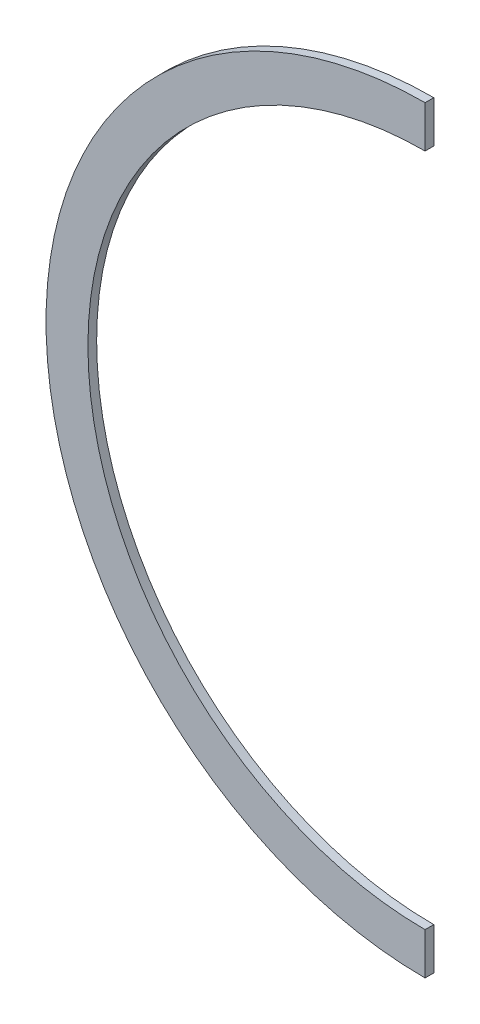
SolidWorks part; units mm, degrees
material "Balsa"
ref_plane "Front Plane" through (0, 0, 0) normal (0, 0, 1) x (1, 0, 0)
ref_plane "Top Plane" through (0, 0, 0) normal (0, 1, 0) x (1, 0, 0)
ref_plane "Right Plane" through (0, 0, 0) normal (1, 0, 0) x (0, 0, -1)
sketch "Sketch1" plane through (0, 0, 0) normal (0, 0, 1) x (1, 0, 0)
  line L0 (0, 0) -> (0, 499.9473) construction
  line L1 (0, -114.7984) -> (0, -129.4545) construction
  line L2 (0, -374.4718) -> (0, 404.2655) construction
  line L3 (-1.651, 142.9921) -> (-1.651, 150.6121) construction
  line L4 (1.651, 142.9921) -> (1.651, 150.6121) construction
  line L5 (-1.651, 142.9921) -> (1.651, 142.9921) construction
  line L6 (136.2041, -53.806) -> (0.0002, 24.7625) construction
  line L7 (-136.2076, -53.7991) -> (0.0002, 24.7625) construction
  line L8 (136.2041, -53.806) -> (0.0002, 24.7625) construction
  line L9 (-136.2076, -53.7991) -> (0.0002, 24.7625) construction
  line L10 (-125.0584, -45.4626) -> (-118.4576, -41.6554) construction
  line L11 (-123.6259, -48.4483) -> (-116.8078, -44.5157) construction
  line L12 (-118.4576, -41.6554) -> (-116.8078, -44.5157) construction
  line L13 (-124.1455, -48.7479) -> (-123.6847, -48.4822) construction
  line L14 (-123.6847, -48.4822) -> (-123.6259, -48.4483) construction
  line L15 (-125.7952, -45.8876) -> (-125.1113, -45.4931) construction
  line L16 (-125.1113, -45.4931) -> (-125.0584, -45.4626) construction
  line L17 (125.4797, -45.7137) -> (125.1075, -45.499) construction
  line L18 (123.8298, -48.5739) -> (123.6807, -48.488) construction
  line L19 (117.0223, -44.647) -> (118.6722, -41.7868) construction
  line L20 (123.6807, -48.488) -> (123.6228, -48.4545) construction
  line L21 (123.6228, -48.4545) -> (117.0223, -44.647) construction
  line L22 (125.1075, -45.499) -> (125.0554, -45.4689) construction
  line L23 (125.0554, -45.4689) -> (118.6722, -41.7868) construction
  line L24 (-107.079, -46.8884) -> (-120.3798, -54.5735)
  line L25 (-108.6638, -44.1348) -> (-121.9647, -51.8199)
  line L28 (-115.4206, -47.9666) -> (-121.9445, -51.7361) construction
  line L29 (-120.2754, -54.5131) -> (-108.646, -44.1245) construction
  line L30 (-114.4607, -49.3188) -> (-122.1124, -53.7399) construction
  line L31 (-113.7686, -50.8257) -> (-120.3665, -54.6379) construction
  line L32 (-115.4206, -47.9666) -> (-113.7686, -50.8257) construction
  line L33 (106.3137, -46.4532) -> (129.9098, -60.0883)
  line L34 (107.9004, -43.7007) -> (131.505, -57.3407)
  line L35 (129.9098, -60.0883) -> (131.505, -57.3407)
  line L36 (129.9098, -60.0883) -> (131.505, -57.3407) construction
  line L37 (107.9004, -43.7007) -> (131.505, -57.3407) construction
  line L38 (106.3137, -46.4532) -> (129.9098, -60.0883) construction
  line L39 (129.9098, -60.0883) -> (107.9004, -43.7007) construction
  line L40 (118.9051, -51.8945) -> (101.8722, -42.0519) construction
  line L41 (120.3631, -54.6438) -> (113.7655, -50.8313)
  line L42 (122.0152, -51.7848) -> (122.0057, -51.7794) construction
  line L43 (113.7655, -50.8313) -> (115.4176, -47.9723)
  line L44 (122.0057, -51.7794) -> (121.9413, -51.7421) construction
  line L45 (121.9413, -51.7421) -> (115.4176, -47.9723)
  line L46 (-108.6638, -44.1348) -> (-121.9647, -51.8199)
  line L47 (-107.079, -46.8884) -> (-120.3798, -54.5735)
  arc A0 (-1.651, 150.6121) -> (-125.0584, -45.4626) centre (0, 12.7) ccw
  circle A1 centre (0, 12.7) radius 120.904
  arc A2 (0, 150.622) -> (-1.651, 150.6121) centre (0, 12.7) ccw
  circle A3 centre (0, 12.7) radius 137.922 construction
  arc A4 (1.651, 150.6121) -> (0, 150.622) centre (0, 12.7) ccw
  arc A5 (-124.3508, -46.9604) -> (-123.6259, -48.4483) centre (0, 12.7) ccw
  arc A6 (-123.6259, -48.4483) -> (-121.9445, -51.7361) centre (0, 12.7) ccw
  arc A7 (-125.0584, -45.4626) -> (-124.3508, -46.9604) centre (0, 12.7) ccw
  arc A8 (124.3477, -46.9667) -> (125.0554, -45.4689) centre (0, 12.7) ccw
  arc A9 (125.0554, -45.4689) -> (1.651, 150.6121) centre (0, 12.7) ccw
  arc A10 (123.6228, -48.4545) -> (124.3477, -46.9667) centre (0, 12.7) ccw
  arc A11 (-121.9153, -51.7914) -> (-121.1641, -53.1919) centre (0, 12.7) ccw
  arc A12 (-120.3665, -54.6379) -> (120.3631, -54.6438) centre (0, 12.7) ccw
  arc A13 (-121.9445, -51.7361) -> (-121.9153, -51.7914) centre (0, 12.7) ccw
  arc A14 (-121.1641, -53.1919) -> (-120.3827, -54.6089) centre (0, 12.7) ccw
  arc A15 (-120.3827, -54.6089) -> (-120.397, -54.5834) centre (0, 12.7) ccw construction
  arc A16 (-120.397, -54.5834) -> (-120.3665, -54.6379) centre (0, 12.7) ccw construction
  arc A17 (120.3936, -54.5893) -> (121.0149, -53.4654) centre (0, 12.7) ccw construction
  arc A18 (121.9413, -51.7421) -> (123.6228, -48.4545) centre (0, 12.7) ccw
  arc A19 (120.3631, -54.6438) -> (120.3936, -54.5893) centre (0, 12.7) ccw construction
  arc A20 (121.0149, -53.4654) -> (121.9121, -51.7974) centre (0, 12.7) ccw construction
  arc A21 (121.9121, -51.7974) -> (121.9413, -51.7421) centre (0, 12.7) ccw construction
  spline S0 degree 3 poles (106.3137, -46.4532) (106.8426, -45.5357) (107.3715, -44.6182) (107.9004, -43.7007) knots 0 0 0 0 1 1 1 1 weights 1 1 1 1
  spline S1 degree 3 poles (-66.0123, 133.6164) (-70.0128, 131.4329) (-73.8716, 129.0699) (-81.3156, 123.9975) (-84.9009, 121.288) (-91.7995, 115.5249) (-95.113, 112.4712) (-99.0811, 108.4341) (-99.866, 107.6157) (-101.4182, 105.9565) (-102.1865, 105.1147) (-104.4569, 102.5643) (-105.9223, 100.8334) (-110.1768, 95.5512) (-115.4725, 88.2691) (-120.0285, 80.5179) (-123.1654, 74.5269) (-124.1643, 72.5002) (-125.5914, 69.415) (-126.0551, 68.3791) (-126.9587, 66.292) (-127.3989, 65.2397) (-129.5278, 59.9684) (-131.0098, 55.7) (-133.5456, 47.0638) (-134.5993, 42.696) (-136.2795, 33.8613) (-136.906, 29.3944) (-137.415, 23.7472) (-137.5031, 22.6146) (-137.6514, 20.3429) (-137.7116, 19.2049) (-137.8496, 15.7999) (-137.8852, 13.5361) (-137.8263, 6.7629) (-137.3062, -2.2197) (-135.9163, -11.1068) (-134.5433, -17.7359) (-134.0304, -19.9395) (-132.8922, -24.3345) (-132.2653, -26.5303) (-130.2347, -33.03) (-128.6774, -37.2656) (-126.1245, -43.2881) (-125.286, -45.1501) (-124.4066, -46.9926) knots 0 0 0 0 0.03125 0.03125 0.0625 0.0625 0.09375 0.09375 0.101563 0.101563 0.109375 0.109375 0.125 0.125 0.15625 0.1875 0.1875 0.203125 0.203125 0.210938 0.210938 0.21875 0.21875 0.25 0.25 0.28125 0.28125 0.3125 0.3125 0.320313 0.320313 0.328125 0.328125 0.34375 0.34375 0.375 0.40625 0.40625 0.421875 0.421875 0.4375 0.4375 0.46875 0.46875 0.48295 0.48295 0.48295 0.48295 construction
  spline S2 degree 3 poles (-1557.5256, 1030.3086) (-495.2142, -0.1753) (-82.1366, -210.7146) (81.4542, -98.9353) (85.033, -96.2237) (91.9188, -90.4573) (95.2258, -87.4025) (99.1858, -83.3647) (99.9691, -82.5461) (101.5182, -80.8868) (102.2849, -80.0449) (104.5506, -77.4941) (106.013, -75.7632) (110.2586, -70.4809) (112.9006, -66.8403) (117.8152, -59.3254) (120.0877, -55.4512) (123.2166, -49.4629) (124.2129, -47.4373) (125.6361, -44.3538) (126.0986, -43.3185) (126.9997, -41.2327) (127.4386, -40.181) (129.5618, -34.9121) (131.0396, -30.646) (133.5674, -22.0152) (134.6173, -17.6505) (136.2906, -8.8227) (136.914, -4.3596) (137.4197, 1.2823) (137.5071, 2.4139) (137.6542, 4.6834) (137.7138, 5.8206) (137.85, 9.2232) (137.8846, 11.4853) (137.8228, 18.2533) (137.2995, 27.2283) (135.9081, 36.1069) (134.5347, 42.7292) (134.0218, 44.9305) (132.8839, 49.3207) (132.2571, 51.5145) (130.2267, 58.0093) (128.67, 62.2416) (125.1615, 70.5162) (123.2097, 74.5586) (118.9108, 82.4534) (116.5637, 86.3058) (113.3753, 90.999) (112.7241, 91.9325) (111.3996, 93.7822) (110.7272, 94.697) (108.6802, 97.4113) (107.2757, 99.181) (102.9447, 104.3725) (96.8571, 110.9816) (90.1513, 116.9722) (84.8861, 121.2292) (83.0917, 122.6088) (80.3399, 124.6181) (79.4113, 125.2786) (77.543, 126.5731) (76.6028, 127.2075) (71.8708, 130.3161) (67.9881, 132.6004) (60.0328, 136.7739) (55.9603, 138.6631) (47.6249, 142.0446) (43.3619, 143.537) (37.9102, 145.1462) (36.8136, 145.4551) (34.6205, 146.0438) (33.5224, 146.3241) (30.2234, 147.1229) (28.0179, 147.5997) (21.3832, 148.8649) (16.9358, 149.4889) (7.993, 150.3014) (3.4975, 150.4899) (-3.2824, 150.4396) (-5.5486, 150.3672) (-10.0934, 150.1088) (-12.3559, 149.9236) (-19.101, 149.2046) (-23.5473, 148.5072) (-32.3412, 146.6856) (-36.6887, 145.5614) (-43.1354, 143.5526) (-45.2718, 142.8291) (-49.5193, 141.273) (-51.6323, 140.4395) (-274.1905, 46.1884) (-224.836, -608.7963) (101.1574, -1839.6029) knots -1.31339 -1.31339 -1.31339 -1.31339 0.03125 0.03125 0.0625 0.0625 0.09375 0.09375 0.101563 0.101563 0.109375 0.109375 0.125 0.125 0.15625 0.15625 0.1875 0.1875 0.203125 0.203125 0.210938 0.210938 0.21875 0.21875 0.25 0.25 0.28125 0.28125 0.3125 0.3125 0.320313 0.320313 0.328125 0.328125 0.34375 0.34375 0.375 0.40625 0.40625 0.421875 0.421875 0.4375 0.4375 0.46875 0.46875 0.5 0.5 0.53125 0.53125 0.539062 0.539062 0.546875 0.546875 0.5625 0.5625 0.59375 0.625 0.625 0.640625 0.640625 0.648437 0.648437 0.65625 0.65625 0.6875 0.6875 0.71875 0.71875 0.75 0.75 0.757812 0.757812 0.765625 0.765625 0.78125 0.78125 0.8125 0.8125 0.84375 0.84375 0.859375 0.859375 0.875 0.875 0.90625 0.90625 0.9375 0.9375 0.953125 0.953125 0.96875 0.96875 2.612134 2.612134 2.612134 2.612134 only from (66.1767, -108.566) to (-66.0123, 133.6164)
  spline S3 degree 3 poles (66.1767, -108.566) (70.1708, -106.3789) (74.0231, -104.0129) (81.4542, -98.9353) (85.033, -96.2237) (91.9188, -90.4573) (95.2258, -87.4025) (99.1858, -83.3647) (99.9691, -82.5461) (101.5182, -80.8868) (102.2849, -80.0449) (104.5506, -77.4941) (106.013, -75.7632) (110.2586, -70.4809) (112.9006, -66.8403) (117.8152, -59.3254) (120.0877, -55.4512) (123.2166, -49.4629) (124.2129, -47.4373) (125.6361, -44.3538) (126.0986, -43.3185) (126.9997, -41.2327) (127.4386, -40.181) (129.5618, -34.9121) (131.0396, -30.646) (133.5674, -22.0152) (134.6173, -17.6505) (136.2906, -8.8227) (136.914, -4.3596) (137.4197, 1.2823) (137.5071, 2.4139) (137.6542, 4.6834) (137.7138, 5.8206) (137.85, 9.2232) (137.8846, 11.4853) (137.8228, 18.2533) (137.2995, 27.2283) (135.9081, 36.1069) (134.5347, 42.7292) (134.0218, 44.9305) (132.8839, 49.3207) (132.2571, 51.5145) (130.2267, 58.0093) (128.67, 62.2416) (125.1615, 70.5162) (123.2097, 74.5586) (118.9108, 82.4534) (116.5637, 86.3058) (113.3753, 90.999) (112.7241, 91.9325) (111.3996, 93.7822) (110.7272, 94.697) (108.6802, 97.4113) (107.2757, 99.181) (102.9447, 104.3725) (96.8571, 110.9816) (90.1513, 116.9722) (84.8861, 121.2292) (83.0917, 122.6088) (80.3399, 124.6181) (79.4113, 125.2786) (77.543, 126.5731) (76.6028, 127.2075) (71.8708, 130.3161) (67.9881, 132.6004) (60.0328, 136.7739) (55.9603, 138.6631) (47.6249, 142.0446) (43.3619, 143.537) (37.9102, 145.1462) (36.8136, 145.4551) (34.6205, 146.0438) (33.5224, 146.3241) (30.2234, 147.1229) (28.0179, 147.5997) (21.3832, 148.8649) (16.9358, 149.4889) (7.993, 150.3014) (3.4975, 150.4899) (-3.2824, 150.4396) (-5.5486, 150.3672) (-10.0934, 150.1088) (-12.3559, 149.9236) (-19.101, 149.2046) (-23.5473, 148.5072) (-32.3412, 146.6856) (-36.6887, 145.5614) (-43.1354, 143.5526) (-45.2718, 142.8291) (-49.5193, 141.273) (-51.6323, 140.4395) (-57.9206, 137.7764) (-62.0153, 135.798) (-66.0123, 133.6164) knots 0 0 0 0 0.03125 0.03125 0.0625 0.0625 0.09375 0.09375 0.101563 0.101563 0.109375 0.109375 0.125 0.125 0.15625 0.15625 0.1875 0.1875 0.203125 0.203125 0.210938 0.210938 0.21875 0.21875 0.25 0.25 0.28125 0.28125 0.3125 0.3125 0.320313 0.320313 0.328125 0.328125 0.34375 0.34375 0.375 0.40625 0.40625 0.421875 0.421875 0.4375 0.4375 0.46875 0.46875 0.5 0.5 0.53125 0.53125 0.539062 0.539062 0.546875 0.546875 0.5625 0.5625 0.59375 0.625 0.625 0.640625 0.640625 0.648437 0.648437 0.65625 0.65625 0.6875 0.6875 0.71875 0.71875 0.75 0.75 0.757812 0.757812 0.765625 0.765625 0.78125 0.78125 0.8125 0.8125 0.84375 0.84375 0.859375 0.859375 0.875 0.875 0.90625 0.90625 0.9375 0.9375 0.953125 0.953125 0.96875 0.96875 1 1 1 1 construction
  spline S4 degree 3 poles (-124.4066, -46.9926) (-124.169, -47.4906) (-123.9283, -47.9871) (-123.6847, -48.4822) knots 0.48295 0.48295 0.48295 0.48295 0.486788 0.486788 0.486788 0.486788 construction
  spline S5 degree 3 poles (-123.6847, -48.4822) (-122.846, -50.1865) (-121.9718, -51.874) (-118.9108, -57.4955) (-116.5612, -61.3517) (-113.369, -66.0497) (-112.7169, -66.9844) (-111.3913, -68.8351) (-110.7184, -69.7503) (-108.6697, -72.4662) (-107.264, -74.2369) (-102.929, -79.4315) (-96.8353, -86.0447) (-90.1214, -92.0392) (-84.8493, -96.299) (-83.0524, -97.6795) (-80.2967, -99.6899) (-79.367, -100.3507) (-77.4971, -101.6451) (-76.5559, -102.2795) (-71.8198, -105.3881) (-67.9332, -107.6723) (-59.9695, -111.8452) (-55.8924, -113.7339) (-47.5468, -117.114) (-43.2782, -118.6053) (-37.8188, -120.2127) (-36.7216, -120.521) (-34.5268, -121.1085) (-33.4279, -121.3881) (-30.1264, -122.185) (-27.9191, -122.6605) (-21.2788, -123.9216) (-16.8274, -124.5426) (-7.8757, -125.3484) (-3.3755, -125.5332) (3.4122, -125.4766) (5.6812, -125.4019) (10.231, -125.1387) (12.493, -124.9512) (19.2413, -124.2249) (23.6899, -123.5224) (32.4889, -121.6898) (36.8393, -120.5597) (43.2904, -118.5412) (45.4283, -117.8143) (48.6163, -116.6419) (49.6759, -116.2374) (51.7885, -115.4006) (52.8426, -114.968) (58.0839, -112.7404) (62.1792, -110.755) (66.1767, -108.566) knots 0.486788 0.486788 0.486788 0.486788 0.5 0.5 0.53125 0.53125 0.539062 0.539062 0.546875 0.546875 0.5625 0.5625 0.59375 0.625 0.625 0.640625 0.640625 0.648437 0.648437 0.65625 0.65625 0.6875 0.6875 0.71875 0.71875 0.75 0.75 0.757812 0.757812 0.765625 0.765625 0.78125 0.78125 0.8125 0.8125 0.84375 0.84375 0.859375 0.859375 0.875 0.875 0.90625 0.90625 0.9375 0.9375 0.953125 0.953125 0.960937 0.960937 0.96875 0.96875 1 1 1 1 construction
  spline S6 degree 3 poles (-108.6638, -44.1348) (-108.1355, -45.0527) (-107.6073, -45.9705) (-107.079, -46.8884) knots 0 0 0 0 1 1 1 1 weights 1 1 1 1
  spline S7 degree 3 poles (-121.9647, -51.8199) (-121.4364, -52.7377) (-120.9081, -53.6556) (-120.3798, -54.5735) knots 0 0 0 0 1 1 1 1 weights 1 1 1 1
  spline S8 degree 3 poles (-893.3226, -1777.9828) (-225.0806, -622.1993) (441.4041, 533.982) (1105.2915, 1689.0999) knots -629.182553 -629.182553 -629.182553 -629.182553 630.825742 630.825742 630.825742 630.825742 weights 1.000316 0.999895 0.999895 1.000316 only from (106.3137, -46.4532) to (107.9004, -43.7007)
  spline S9 degree 3 poles (-121.8597, -51.7592) (-121.5948, -52.2177) (-121.3299, -52.6762) (-121.065, -53.1347) knots 0 0 0 0 0.5 0.5 0.5 0.5 weights 1 1 1 1 construction
  spline S12 degree 3 poles (-1117.6926, 1681.4946) (-455.9021, 527.2867) (209.8433, -629.4163) (878.1921, -1786.2645) knots -630.157908 -630.157908 -630.157908 -630.157908 629.848871 629.848871 629.848871 629.848871 weights 1.000509 0.999831 0.99983 1.000507 only from (-121.9647, -51.8199) to (-120.3798, -54.5735)
  spline S13 degree 3 poles (-1104.4721, 1689.253) (-442.507, 534.8951) (223.2028, -621.8101) (891.4356, -1778.7423) knots -630.135261 -630.135261 -630.135261 -630.135261 629.876801 629.876801 629.876801 629.876801 weights 1.000459 0.999847 0.999847 1.000457 only from (-108.6638, -44.1348) to (-107.079, -46.8884)
  point P7 (0, -125.5003)
  point P8 (0, 150.4602)
  point P25 (-125.0584, -45.4626)
  point P38 (123.6228, -48.4545)
  dimension "D2" = 275.844
  dimension "D1" = 275.9605
  dimension "D3" = 12.7
  dimension "D5" = 3.302
  dimension "D6" = 7.62
  dimension "D7" = 3.302
  dimension "D8" = 7.62
  dimension "D9" = 3.302
  dimension "D10" = 7.62
  dimension "D11" = 3.302
  dimension "D12" = 7.62
  dimension "D13" = 3.302
  dimension "D14" = 7.62
  dimension "D4" = 17.018
extrude "Boss-Extrude1" [suppressed] add sketch "Sketch1" along normal mid plane 3.175
sketch "Sketch2" plane through (248.2736, -245.0135, 0) normal (0, 0, -1) x (0, -1, 0)
  line L3 (-245.0135, 248.2736) -> (-427.6569, 248.2736) construction
  circle A1 centre (-257.7135, 248.2736) radius 137.922
  circle A16 centre (-257.7135, 248.2736) radius 122.682
  dimension "D1" = 12.7
  dimension "D2" = 275.844
  dimension "D3" = 15.24
fillet "Fillet1" [suppressed] radius 1.27
extrude "Boss-Extrude2" add sketch "Sketch2" along normal mid plane 3.175
sketch "Sketch3" plane through (0, 0, 0) normal (1, 0, 0) x (0, 0, -1)
  line L1 (-141.282, 263.3615) -> (149.6958, 263.3615)
  line L2 (-141.282, 263.3615) -> (-141.282, -241.4673)
  line L3 (-141.282, -241.4673) -> (149.6958, -241.4673)
  line L4 (149.6958, 263.3615) -> (149.6958, -241.4673)
extrude "Cut-Extrude1" cut sketch "Sketch3" along normal through all
equation "\"slotwidth\"=0.13"
equation "\"D11@Sketch1\"=\"slotwidth\""
